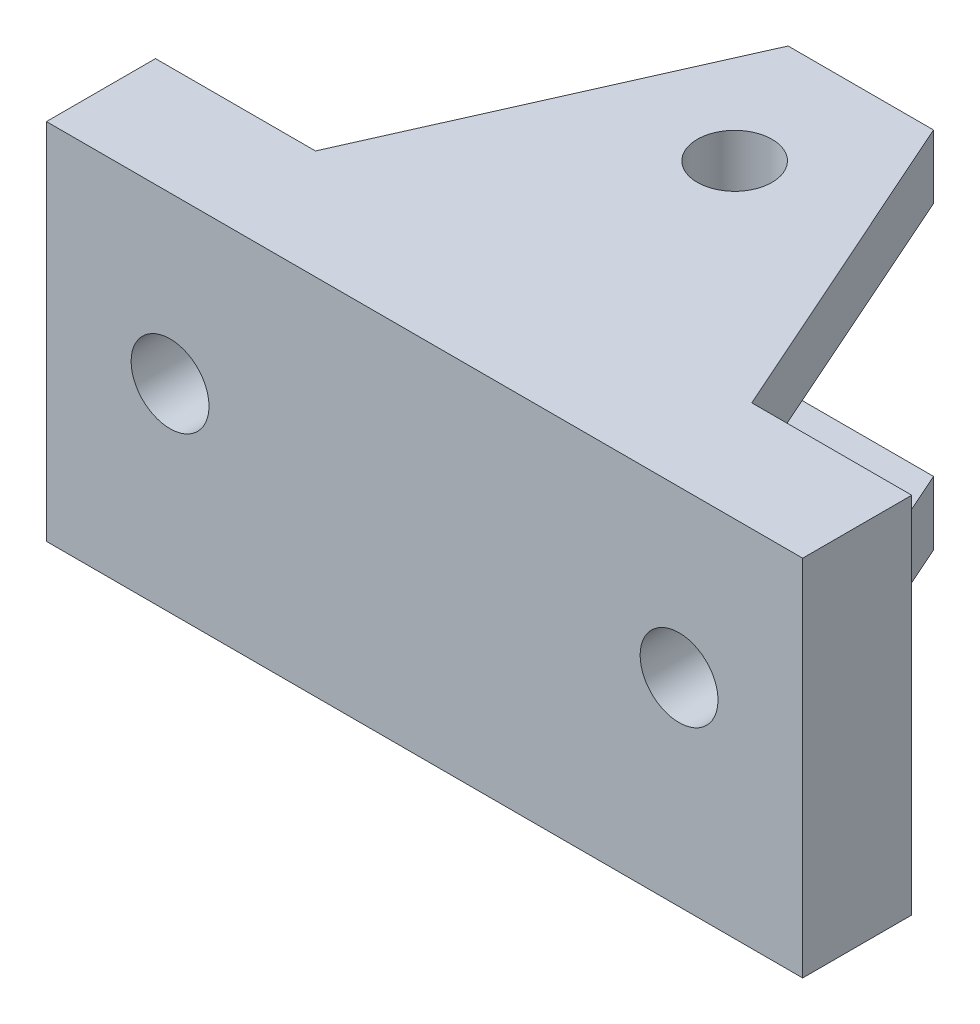
SolidWorks part; units mm, degrees
material "Custom Plastic"
ref_plane "X-Y Datum" through (0, 0, 0) normal (0, 0, 1) x (1, 0, 0)
ref_plane "X-Z Datum" through (0, 0, 0) normal (0, 1, 0) x (1, 0, 0)
ref_plane "Y-Z Datum" through (0, 0, 0) normal (1, 0, 0) x (0, 0, -1)
sketch "Sketch1" plane through (0, 0, 0) normal (1, 0, 0) x (0, 0, -1)
  line L0 (0, 8.7126) -> (0, 40.4626)
  line L1 (0, 40.4626) -> (39.7797, 40.4626)
  line L2 (39.7797, 40.4626) -> (39.7797, 34.9127)
  line L3 (39.7797, 34.9127) -> (9.525, 34.9127)
  line L4 (9.525, 34.9127) -> (9.525, 14.2625)
  line L5 (9.525, 14.2625) -> (39.7797, 14.2625)
  line L6 (39.7797, 14.2625) -> (39.7797, 8.7126)
  line L7 (39.7797, 8.7126) -> (0, 8.7126)
  line L8 (29.6197, 40.4626) -> (29.6197, 8.7126) construction
  line L9 (0, 26.0299) -> (9.525, 26.0299) construction
  line L10 (0, 22.0299) -> (0, 30.0299) construction
  circle A0 centre (29.6197, 24.5876) radius 10.3251 construction
  point P15 (0, 0)
  point P19 (0, 0)
  dimension "D5" = 20.6502
  dimension "D1" = 20.6502
  dimension "D2" = 31.75
  dimension "D3" = 10.16
  dimension "D4" = 9.525
extrude "Boss-Extrude1" add sketch "Sketch1" along normal blind 76.2
sketch "Sketch2" plane through (0, 0, -9.525) normal (0, 0, -1) x (-1, 0, 0)
  line L0 (-38.1, 34.9127) -> (-38.1, 14.2625) construction
  line L1 (-76.2, 34.9127) -> (0, 34.9127) construction
  line L2 (-76.2, 14.2625) -> (0, 14.2625) construction
  line L3 (-60.325, 26.0299) -> (-15.875, 26.0299) construction
  circle A0 centre (-60.325, 26.0299) radius 3.4
  circle A1 centre (-15.875, 26.0299) radius 3.4
  point P8 (-38.1, 26.0299)
  dimension "D2" = 6.8
  dimension "D1" = 44.45
extrude "Cut-Extrude1" cut sketch "Sketch2" against normal up to surface (9.525 mm away) up to face at (38.1, 24.5876, 0)
sketch "Sketch3" plane through (0, 40.4626, 0) normal (0, 1, 0) x (1, 0, 0)
  line L0 (76.2, 39.7797) -> (0, 39.7797) construction
  line L1 (31.75, 38.1) -> (19.05, 9.525)
  line L2 (44.45, 38.1) -> (57.15, 9.525)
  line L3 (31.75, 38.1) -> (44.45, 38.1)
  line L4 (0, 39.7797) -> (0, 9.525)
  line L5 (0, 0) -> (0, 39.7797) construction
  line L6 (0, 9.525) -> (19.05, 9.525)
  line L7 (0, 39.7797) -> (76.2, 39.7797)
  line L8 (76.2, 39.7797) -> (76.2, 9.525)
  line L9 (76.2, 39.7797) -> (76.2, 0) construction
  line L10 (76.2, 9.525) -> (57.15, 9.525)
  line L12 (76.2, 0) -> (0, 0) construction
  circle A0 centre (38.1, 27.0797) radius 3.2639
  point P4 (38.1, 39.7797)
  point P19 (13.2606, 9.525)
  point P20 (19.2705, 9.525)
  dimension "D1" = 6.5278
  dimension "D2" = 12.7
  dimension "D3" = 12.7
  dimension "D4" = 38.1
  dimension "D5" = 19.05
extrude "Cut-Extrude2" cut sketch "Sketch3" against normal up to surface (31.75 mm away) up to face at (38.1, 8.7126, -19.8899)
sketch "Sketch4" plane through (0, 0, -9.525) normal (0, 0, -1) x (-1, 0, 0)
  line L0 (0, 40.4626) -> (-19.05, 40.4626) construction
  line L1 (0, 8.7126) -> (-5.08, 8.7126)
  line L2 (0, 8.7126) -> (0, 40.4626)
  line L3 (0, 40.4626) -> (-5.08, 40.4626)
  line L4 (-5.08, 8.7126) -> (-5.08, 40.4626)
  line L5 (-57.15, 40.4626) -> (-76.2, 40.4626) construction
  line L6 (-76.2, 8.7126) -> (-71.12, 8.7126)
  line L7 (-76.2, 8.7126) -> (-76.2, 40.4626)
  line L8 (-76.2, 40.4626) -> (-71.12, 40.4626)
  line L9 (-71.12, 8.7126) -> (-71.12, 40.4626)
  dimension "D1" = 5.08
extrude "Cut-Extrude3" cut sketch "Sketch4" against normal up to surface (9.525 mm away) up to face at (60.325, 29.4299, 0)
